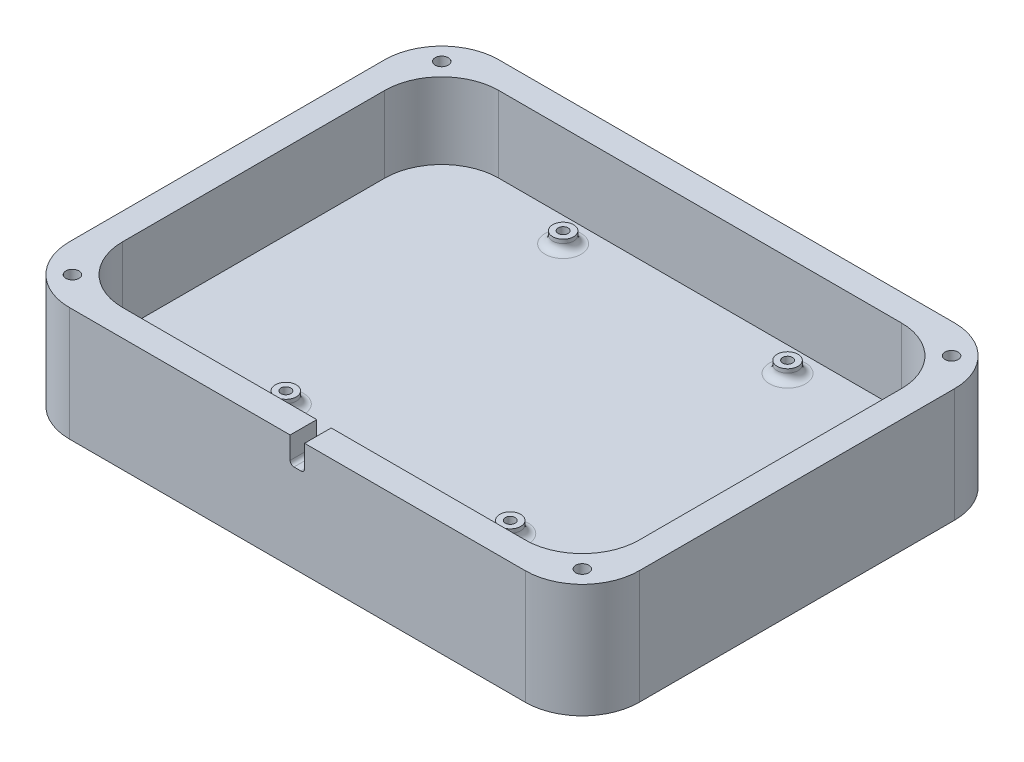
SolidWorks part; units mm, degrees
ref_plane "Front Plane" through (0, 0, 0) normal (0, 0, 1) x (1, 0, 0)
ref_plane "Top Plane" through (0, 0, 0) normal (0, 1, 0) x (1, 0, 0)
ref_plane "Right Plane" through (0, 0, 0) normal (1, 0, 0) x (0, 0, -1)
sketch "Sketch1" plane through (0, 0, 0) normal (0, 1, 0) x (1, 0, 0)
  line L1 (-75, 50) -> (75, 50)
  line L2 (-75, 50) -> (-75, -50)
  line L3 (-75, -50) -> (75, -50)
  line L4 (75, 50) -> (75, -50)
  line L5 (-75, 50) -> (75, -50) construction
  line L6 (-75, -50) -> (75, 50) construction
  point P0 (0, 0)
  dimension "D1" = 150
  dimension "D2" = 100
extrude "Boss-Extrude1" add sketch "Sketch1" along normal blind 10
sketch "Sketch2" plane through (0, 10, 0) normal (0, 1, 0) x (1, 0, 0)
  line L0 (75, -50) -> (75, 50) construction
  line L1 (0, 0) -> (0, 70.2566) construction
  line L2 (75, 50) -> (-75, 50) construction
  line L3 (0, 0) -> (146.4068, 0) construction
  circle A1 centre (29.54, 36.5) radius 2.75
  circle A2 centre (29.54, -36.5) radius 2.75
  circle A3 centre (-29.54, -36.5) radius 2.75
  circle A4 centre (-29.54, 36.5) radius 2.75
  point P0 (29.54, 36.5)
  point P8 (-29.54, -36.5)
  point P9 (29.54, -36.5)
  point P16 (-29.54, 36.5)
  dimension "D5" = 5.5
  dimension "D1" = 45.46
  dimension "D2" = 13.5
extrude "Boss-Extrude2" add sketch "Sketch2" along normal blind 3
hole_wizard "Ø1.0mm Dowel Hole1" positions "Sketch3" profile "Sketch4" hole size "Ø1.0" standard "ISO"
sketch "Sketch3" plane through (0, 13, 0) normal (0, 1, 0) x (1, 0, 0)
  point P0 (-29.54, 36.5)
  point P3 (29.54, 36.5)
  point P6 (29.54, -36.5)
  point P9 (-29.54, -36.5)
sketch "Sketch4" plane through (-29.54, 13, -36.5) normal (1, 0, 0) x (0, 0, 1)
  line L0 (0, 0) -> (0, 10.7811)
  line L1 (0, 10.7811) -> (1.3, 10)
  line L2 (1.3, 10) -> (1.3, 0)
  line L5 (1.3, 0) -> (0, 0)
  line L10 (0, 10.7811) -> (-1.3, 10) construction
  line L11 (0, -6.35) -> (0, 107.95) construction
  dimension "Hole Dia." = 2.6
  dimension "Hole Depth" = 10
  dimension "Drill Angle" = 118
fillet "Fillet1" radius 2 4 edges at (29.54, 10, 33.75) (-29.54, 10, 39.25) (29.54, 10, -33.75) (-29.54, 10, -39.25)
sketch "Sketch5" plane through (0, 0, 0) normal (0, -1, 0) x (1, 0, 0)
  line L1 (-75, 50) -> (75, 50)
  line L2 (-75, 50) -> (-75, 63)
  line L3 (-75, 63) -> (75, 63)
  line L4 (75, 50) -> (75, 63)
  dimension "D1" = 13
extrude "Boss-Extrude3" add sketch "Sketch5" against normal blind 10
sketch "Sketch7" plane through (0, 10, 0) normal (0, 1, 0) x (1, 0, 0)
  line L1 (-75, 50) -> (75, 50)
  line L2 (-75, 50) -> (-75, -63)
  line L3 (-75, -63) -> (75, -63)
  line L4 (75, 50) -> (75, -63)
extrude "Extrude-Thin1" add sketch "Sketch7" along normal blind 20 thin thin type one direction reverse wall 7
sketch "Sketch8" plane through (0, 0, 63) normal (0, 0, 1) x (1, 0, 0)
  line L0 (0, 30) -> (0, 23.2) construction
  line L1 (-75, 30) -> (75, 30) construction
  line L2 (-1.9, 30) -> (1.9, 30)
  line L3 (1.9, 30) -> (1.9, 24.2)
  line L4 (0.9, 23.2) -> (-0.9, 23.2)
  line L5 (-1.9, 30) -> (-1.9, 24.2)
  arc A0 (1.9, 24.2) -> (0.9, 23.2) centre (0.9, 24.2) cw
  arc A1 (-1.9, 24.2) -> (-0.9, 23.2) centre (-0.9, 24.2) ccw
  dimension "D2" = 1
  dimension "D1" = 1.9
  dimension "D3" = 5.8
extrude "Cut-Extrude1" cut sketch "Sketch8" against normal up to next
fillet "Fillet2" radius 15 4 edges at (75, 15, 63) (75, 15, -50) (-75, 15, -50) (-75, 15, 63)
fillet "Fillet3" radius 15 4 edges at (-68, 20, -43) (-68, 20, 56) (68, 20, -43) (68, 20, 56)
sketch "Sketch9" plane through (0, 30, 0) normal (0, 1, 0) x (1, 0, 0)
  line L0 (-63.6066, 38.6066) -> (-70.6066, 45.6066) construction
  line L1 (-75, -6.5) -> (75, -6.5) construction
  line L2 (-75, 35) -> (-75, -48) construction
  line L3 (75, -48) -> (75, 35) construction
  line L4 (0, 50) -> (0, -63) construction
  line L5 (60, 50) -> (-60, 50) construction
  line L6 (-0.9, -63) -> (0.9, -63) construction
  arc A0 (-53, 43) -> (-68, 28) centre (-53, 28) ccw construction
  arc A1 (-60, 50) -> (-75, 35) centre (-60, 35) ccw construction
  circle A2 centre (-67.1066, 42.1066) radius 1.725
  circle A3 centre (67.1066, 42.1066) radius 1.725
  circle A4 centre (67.1066, -55.1066) radius 1.725
  circle A5 centre (-67.1066, -55.1066) radius 1.725
  dimension "D1" = 3.45
extrude "Cut-Extrude2" cut sketch "Sketch9" against normal blind 6
